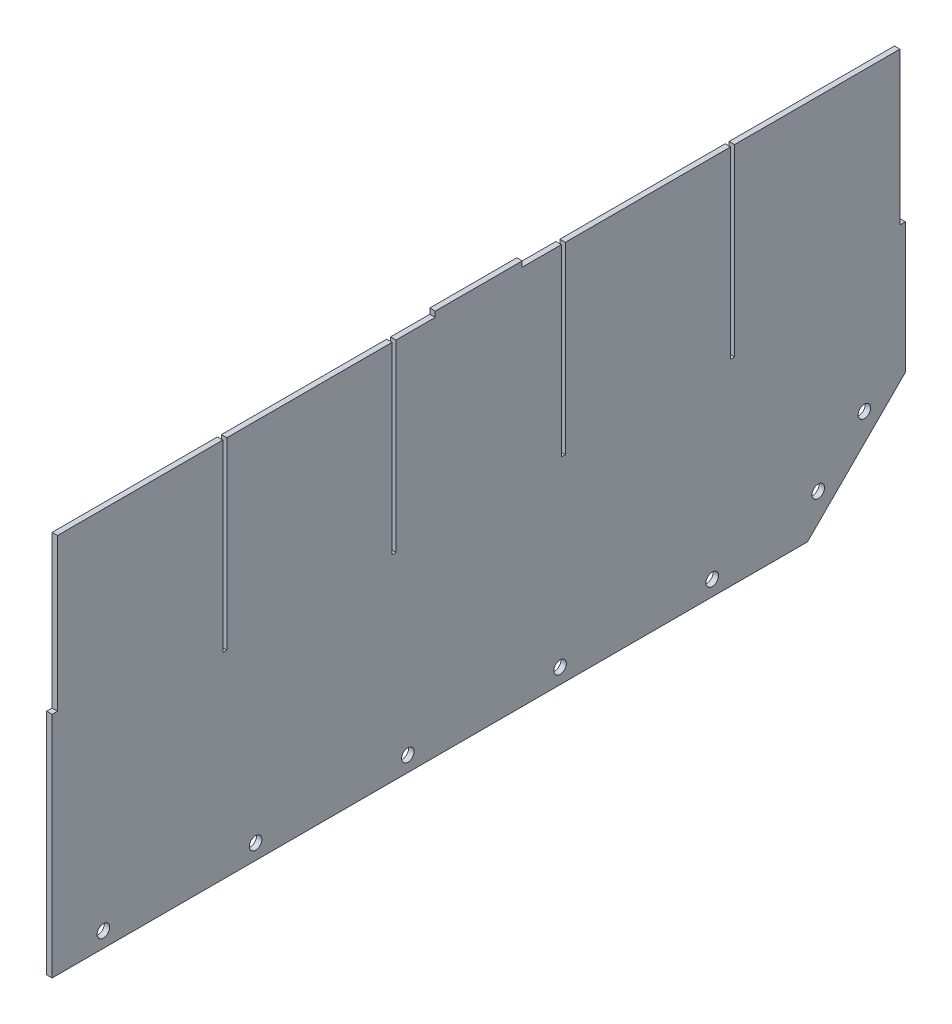
SolidWorks part; units mm, degrees
material "6061-T6 (SS)"
ref_plane "X-Y Datum" through (0, 0, 0) normal (0, 0, 1) x (1, 0, 0)
ref_plane "X-Z Datum" through (0, 0, 0) normal (0, 1, 0) x (1, 0, 0)
ref_plane "Y-Z Datum" through (0, 0, 0) normal (1, 0, 0) x (0, 0, -1)
sketch "Sketch1" plane through (0, 0, 0) normal (1, 0, 0) x (0, 0, -1)
  line L1 (-249.174, 82.55) -> (249.174, 82.55)
  line L2 (-249.174, 82.55) -> (-249.174, -82.55)
  line L3 (-249.174, -82.55) -> (249.174, -82.55)
  line L4 (249.174, 82.55) -> (249.174, -82.55)
  line L5 (-249.174, 82.55) -> (249.174, -82.55) construction
  line L6 (-249.174, -82.55) -> (249.174, 82.55) construction
  point P0 (0, 0)
  dimension "D1" = 165.1
  dimension "D2" = 498.348
extrude "Boss-Extrude1" add sketch "Sketch1" along normal mid plane 3.175
sketch "Sketch2" plane through (1.5875, 0, 0) normal (1, 0, 0) x (0, 0, -1)
  line L3 (192.024, -139.7) -> (-249.174, -139.7)
  line L5 (-249.174, -82.55) -> (249.174, -82.55) construction
  line L6 (-249.174, -82.55) -> (249.174, -82.55)
  line L7 (-249.174, -82.55) -> (-249.174, -139.7)
  line L12 (192.024, -139.7) -> (249.174, -82.55)
  line M10 (-249.174, -82.55) -> (249.174, -82.55)
  dimension "D1" = 45
  dimension "D5" = 57.15
extrude "Boss-Extrude2" add sketch "Sketch2" against normal blind 3.175 contours L3 L12 M10 region at (1.5875, -110.5456, 13.9978)
sketch "Sketch3" plane through (1.5875, 0, 0) normal (1, 0, 0) x (0, 0, -1)
  line L0 (-219.202, -139.7) -> (-219.202, -130.81)
  line L1 (192.024, -139.7) -> (-249.174, -139.7) construction
  line L2 (-219.202, -130.81) -> (-249.174, -130.81)
  line L3 (-249.174, 82.55) -> (-249.174, -139.7) construction
  circle A0 centre (-219.202, -130.81) radius 3.675
  dimension "D1" = 29.972
  dimension "D2" = 8.89
extrude "Cut-Extrude1" cut sketch "Sketch3" against normal blind 3.175 contours L2 A0 L0 | L0 A0 L2 region at (1.5875, -132.3697, 220.7617) region at (1.5875, -130.2901, 218.6821)
pattern_linear "LPattern1" count 5 spacing 88.9 along (0, 0, -1) of "Cut-Extrude1"
sketch "Sketch4" plane through (1.5875, 0, 0) normal (1, 0, 0) x (0, 0, -1)
  line L0 (192.024, -139.7) -> (183.9418, -131.6178)
  line L1 (183.9418, -131.6178) -> (198.3102, -117.2494)
  circle A0 centre (198.3102, -117.2494) radius 3.675
extrude "Cut-Extrude2" cut sketch "Sketch4" against normal through all contours A0 region at (1.5875, -120.5486, -199.6768)
pattern_linear "LPattern2" count 2 spacing 38.1 along (0, 0.7071, -0.7071) of "Cut-Extrude2"
sketch "Sketch5" plane through (-1.5875, 0, 0) normal (-1, 0, 0) x (0, 0, 1)
  line L1 (-249.174, 82.55) -> (-245.999, 82.55)
  line L2 (-249.174, 82.55) -> (-249.174, -6.35)
  line L3 (-249.174, -6.35) -> (-245.999, -6.35)
  line L4 (-245.999, 82.55) -> (-245.999, -6.35)
  line L5 (249.174, 82.55) -> (245.999, 82.55)
  line L6 (249.174, 82.55) -> (249.174, -6.35)
  line L7 (249.174, -6.35) -> (245.999, -6.35)
  line L8 (245.999, 82.55) -> (245.999, -6.35)
  dimension "D1" = 3.175
  dimension "D2" = 88.9
  dimension "D3" = 3.175
  dimension "D4" = 88.9
extrude "Cut-Extrude3" cut sketch "Sketch5" against normal through all
sketch "Sketch6" plane through (-1.5875, 0, 0) normal (-1, 0, 0) x (0, 0, 1)
  line L0 (-122.174, 82.55) -> (-249.174, 82.55) construction
  line L1 (-149.4282, 82.55) -> (-149.4282, -24.892) construction
  line L2 (-122.174, 82.55) -> (-249.174, 82.55)
  line L3 (-149.4282, 82.55) -> (-149.4282, -24.892)
  line L5 (-149.4282, 82.55) -> (-147.1422, 82.55)
  line L6 (-149.4282, 82.55) -> (-149.4282, -24.892)
  line L7 (-149.4282, -24.892) -> (-147.1422, -24.892)
  line L8 (-147.1422, 82.55) -> (-147.1422, -24.892)
  dimension "D1" = 2.286
  dimension "D2" = 107.442
extrude "Cut-Extrude4" cut sketch "Sketch6" against normal through all contours L8 L2 L3 L7 region at (-1.5875, 28.829, -148.2852)
pattern_linear "LPattern3" count 4 spacing 98.8568 along (0, 0, 1) of "Cut-Extrude4"
sketch "Sketch7" plane through (-1.5875, 0, 0) normal (-1, 0, 0) x (0, 0, 1)
  line L0 (122.174, 85.725) -> (25.4, 85.725) construction
  line L1 (25.4, 82.55) -> (-25.4, 82.55)
  line L2 (25.4, 82.55) -> (25.4, 85.725)
  line L3 (25.4, 85.725) -> (-25.4, 85.725)
  line L4 (-25.4, 82.55) -> (-25.4, 85.725)
  line L5 (25.4, 82.55) -> (-25.4, 85.725) construction
  line L6 (25.4, 85.725) -> (-25.4, 82.55) construction
  point P0 (0, 84.1375)
  point P5 (-1.1535, 83.6732)
  point P8 (0, 0)
  dimension "D1" = 3.175
  dimension "D2" = 50.8
extrude "Boss-Extrude3" add sketch "Sketch7" against normal blind 3.175
